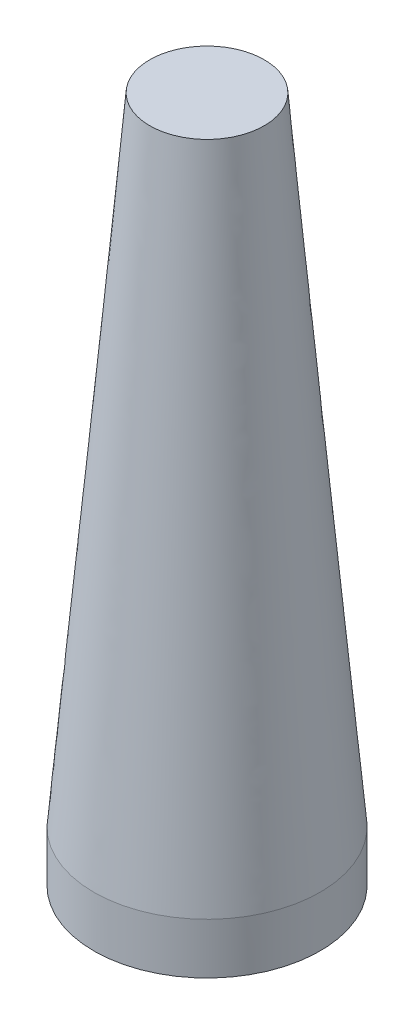
SolidWorks part; units mm, degrees
ref_plane "Front Plane" through (0, 0, 0) normal (0, 0, 1) x (1, 0, 0)
ref_plane "Top Plane" through (0, 0, 0) normal (0, 1, 0) x (1, 0, 0)
ref_plane "Right Plane" through (0, 0, 0) normal (1, 0, 0) x (0, 0, -1)
sketch "Sketch1" plane through (0, 0, 0) normal (0, 1, 0) x (1, 0, 0)
  circle A0 centre (0, 0) radius 22.25
  dimension "D1" = 44.5
ref_plane "Plane1" through (0, 125, 0) normal (0, 1, 0) x (1, 0, 0)
sketch "Sketch2" plane through (0, 125, 0) normal (0, 1, 0) x (1, 0, 0)
  circle A0 centre (0, 0) radius 11.25
  dimension "D1" = 22.5
loft "Loft1" add profiles "Sketch2", "Sketch1" connector at (-7.6857, 125, 8.2154) connector at (-11.9811, 0, 18.7487)
sketch "Sketch3" plane through (0, 0, 0) normal (0, -1, 0) x (1, 0, 0)
  circle A0 centre (0, 0) radius 13.75
  dimension "D1" = 27.5
ref_plane "Plane2" through (0, 115, 0) normal (0, -1, 0) x (-1, 0, 0)
sketch "Sketch4" plane through (0, 115, 0) normal (0, -1, 0) x (-1, 0, 0)
  circle A0 centre (0, 0) radius 5
  dimension "D1" = 10
loft "Cut-Loft1" cut profiles "Sketch4", "Sketch3" connector at (4.2681, 115, -2.6045) connector at (13.635, 0, -1.7747)
sketch "Sketch5" plane through (0, 0, 0) normal (0, -1, 0) x (1, 0, 0)
  circle A0 centre (0, 0) radius 13.75 construction
  circle A1 centre (0, 0) radius 22.25 construction
  circle A2 centre (0, 0) radius 13.75
  circle A3 centre (0, 0) radius 22.25
extrude "Boss-Extrude1" add sketch "Sketch5" along normal blind 10
